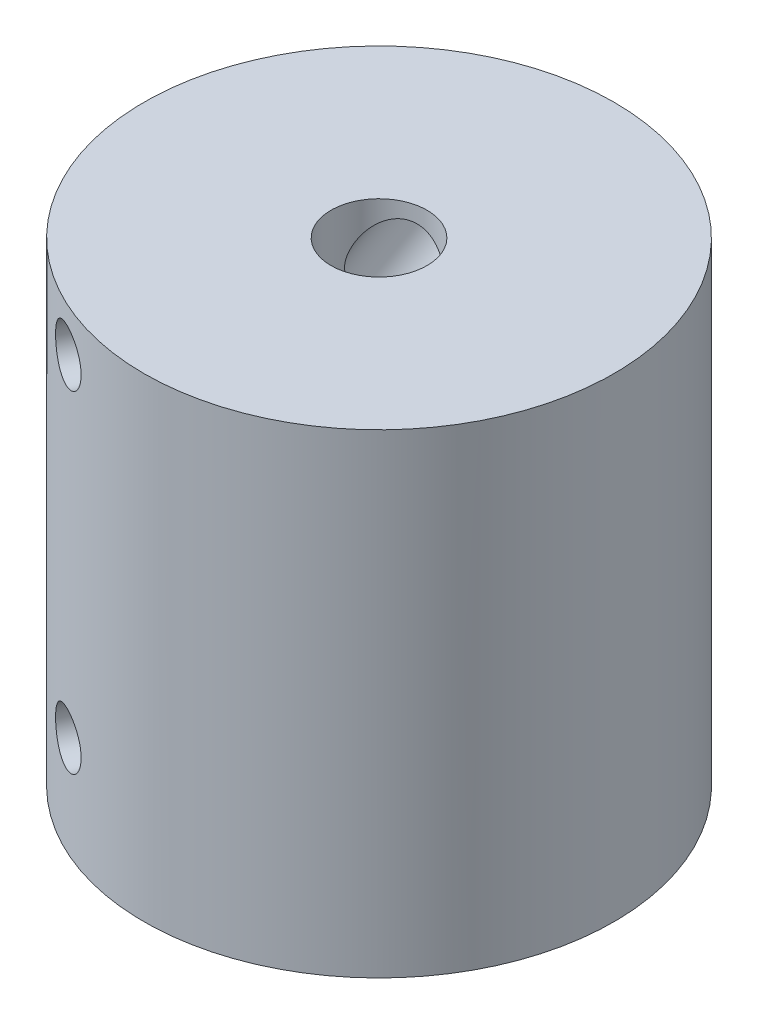
SolidWorks part; units mm, degrees
ref_plane "Front Plane" through (0, 0, 0) normal (0, 0, 1) x (1, 0, 0)
ref_plane "Top Plane" through (0, 0, 0) normal (0, 1, 0) x (1, 0, 0)
ref_plane "Right Plane" through (0, 0, 0) normal (1, 0, 0) x (0, 0, -1)
sketch "Sketch2" plane through (0, 0, 0) normal (0, 1, 0) x (1, 0, 0)
  circle A0 centre (0, 0) radius 2.4447
  circle A1 centre (0, 0) radius 11.9697
  dimension "D1" = 4.8895
  dimension "D2" = 23.9395
extrude "Boss-Extrude1" add sketch "Sketch2" along normal blind 5.588
ref_point "Point1" parameters "D1"=14.2875
ref_plane "Plane1" through (-1.0392, 0, 2.2129) normal (0.4251, 0, -0.9052) x (-0.9052, 0, -0.4251)
sketch "Sketch3" plane through (-1.0392, 0, 2.2129) normal (0.4251, 0, -0.9052) x (-0.9052, 0, -0.4251)
  line L0 (-11.9698, 0) -> (11.9698, 0) construction
  circle A0 centre (0, 3.302) radius 1.3526
  point P4 (0, 0)
  point P5 (0, 0)
  dimension "D2" = 2.7051
  dimension "D1" = 3.302
extrude "Cut-Extrude1" cut sketch "Sketch3" against normal blind 15 and the other way blind 2.54
sketch "Sketch4" plane through (0, 0, 0) normal (0, -1, 0) x (-1, 0, 0)
  circle A0 centre (0, 0) radius 11.9697
  dimension "D1" = 23.9395
extrude "Boss-Extrude2" add sketch "Sketch4" along normal blind 18.588
sketch "Sketch5" plane through (0, -18.588, 0) normal (0, -1, 0) x (-1, 0, 0)
  circle A0 centre (0, 0) radius 2.5635
  dimension "D1" = 5.127
extrude "Cut-Extrude3" cut sketch "Sketch5" against normal blind 12
sketch "Sketch6" plane through (-1.0392, 0, 2.2129) normal (0.4251, 0, -0.9052) x (-0.9052, 0, -0.4251)
  line L0 (-11.9698, -18.588) -> (11.9698, -18.588) construction
  circle A0 centre (0, -13.588) radius 1.3525
  point P2 (0, 0)
  point P3 (0, 0)
  point P5 (0, 0)
  point P6 (0, 0)
  dimension "D1" = 2.7051
  dimension "D2" = 5
extrude "Cut-Extrude4" cut sketch "Sketch6" against normal blind 12.446 and the other way blind 1.27
ref_plane "Plane2" through (-4.0635, 0, -11.2589) normal (-0.3395, 0, -0.9406) x (0, -1, 0)
ref_axis "Axis1" through (0, 5.588, 0) along (0, -1, 0)
ref_plane "Plane3" through (0, 0, 0) normal (0.9406, 0, -0.3395) x (0, -1, 0)
sketch "Sketch10" plane through (-4.0635, 0, -11.2589) normal (-0.3395, 0, -0.9406) x (0, -1, 0)
  line L0 (-13.2968, 0) -> (13.2968, 0) construction
  line L1 (18.588, -11.9697) -> (18.588, 11.9697) construction
  line L2 (-5.588, 11.9697) -> (-5.588, -11.9697) construction
  circle A0 centre (13.762, 0) radius 2.0193
  circle A1 centre (-2.794, 0) radius 2.0193
  point P4 (0, 0)
  point P7 (0, 0)
  dimension "D1" = 4.0386
  dimension "D2" = 4.0386
  dimension "D3" = 4.826
  dimension "D4" = 2.794
extrude "Cut-Extrude6" cut sketch "Sketch10" against normal blind 11.43
